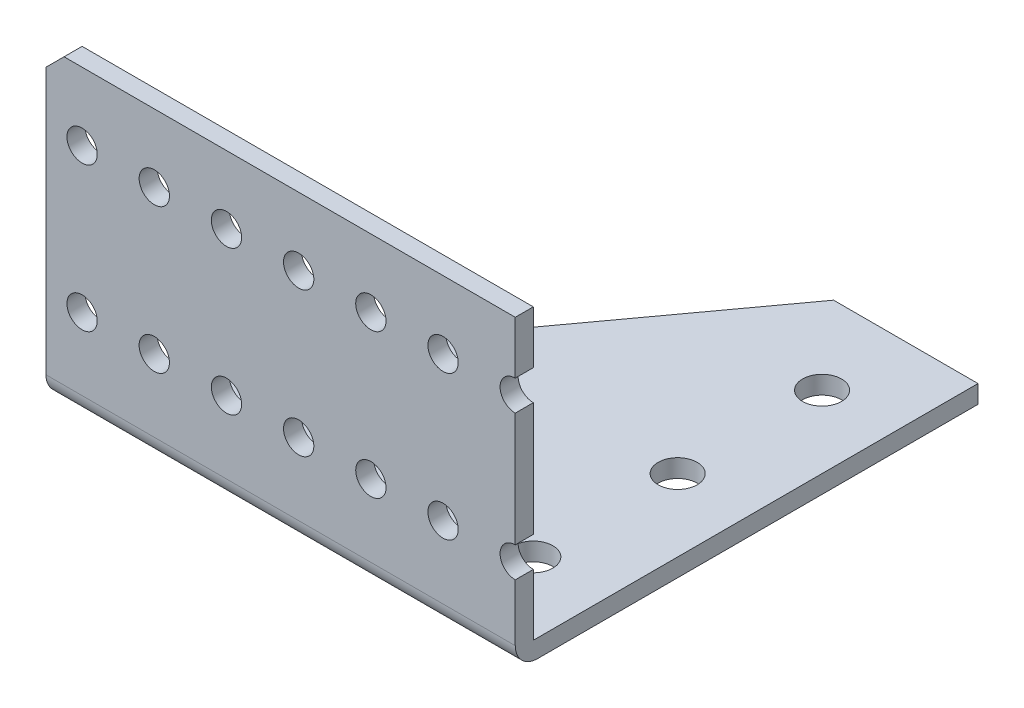
SolidWorks part; units mm, degrees
ref_plane "Front Plane" through (0, 0, 0) normal (0, 0, 1) x (1, 0, 0)
ref_plane "Top Plane" through (0, 0, 0) normal (0, 1, 0) x (1, 0, 0)
ref_plane "Right Plane" through (0, 0, 0) normal (1, 0, 0) x (0, 0, -1)
sketch "Sketch1" plane through (0, 0, 0) normal (0, 1, 0) x (1, 0, 0)
  line L0 (41.275, -40.7035) -> (41.275, 40.7035)
  line L1 (41.275, 40.7035) -> (-41.275, 40.7035)
  line L3 (-41.275, -40.7035) -> (-41.275, 40.7035)
  line L4 (-41.275, -40.7035) -> (41.275, -40.7035)
  line L5 (41.275, 40.7035) -> (-41.275, -40.7035) construction
  line L6 (0, -55) -> (0, 55) construction
  line L7 (-55, 0) -> (55, 0) construction
  point P2 (0, 0)
  dimension "D2" = 81.407
  dimension "D1" = 82.55
extrude "Boss-Extrude1" add sketch "Sketch1" along normal blind 3.175 from offset 34.925 offset against normal yes
sketch "Sketch3" plane through (0, -31.75, 0) normal (0, 1, 0) x (1, 0, 0)
  line L0 (41.275, -40.7035) -> (-41.275, -40.7035)
  line L1 (-41.275, -40.7035) -> (-41.275, -37.5285)
  line L2 (-41.275, -37.5285) -> (41.275, -37.5285)
  line L3 (-41.275, -40.7035) -> (41.275, -40.7035) construction
  line L4 (41.275, -40.7035) -> (41.275, -37.5285)
  line L5 (-41.275, 40.7035) -> (-41.275, -40.7035) construction
  line L6 (41.275, -40.7035) -> (41.275, 40.7035) construction
  point P0 (0, 0)
  dimension "D1" = 3.175
extrude "Boss-Extrude2" add sketch "Sketch3" along normal blind 50.8
hole_wizard "#10 Clearance Hole2" positions "Sketch7" profile "Sketch6" hole size "#10" standard "ANSI Inch" end condition through all
sketch "Sketch7" plane through (0, 0, -40.7035) normal (0, 0, -1) x (-1, 0, 0)
  line L2 (-41.275, -18.288) -> (34.925, -18.288) construction
  line L5 (-41.275, 7.112) -> (34.925, 7.112) construction
  line L8 (41.275, 19.05) -> (41.275, -31.75) construction
  line L9 (-41.275, 19.05) -> (-41.275, -31.75) construction
  line L10 (-41.275, 19.05) -> (41.275, 19.05) construction
  point P56 (22.225, 7.112)
  point P57 (9.525, 7.112)
  point P58 (-3.175, 7.112)
  point P59 (-15.875, 7.112)
  point P61 (-28.575, 7.112)
  point P118 (22.225, -18.288)
  point P119 (9.525, -18.288)
  point P120 (-3.175, -18.288)
  point P121 (-15.875, -18.288)
  point P123 (-28.575, -18.288)
  point P157 (34.925, 7.112)
  point P159 (34.925, -18.288)
  point P185 (-41.275, 7.112)
  point P189 (-41.275, -18.288)
  point P192 (-28.575, -18.161)
  point P198 (-41.275, -18.161)
  point P199 (-41.275, 7.239)
  point P200 (0, 0)
  point P201 (0, 0)
  dimension "D1" = 6.35
  dimension "D2" = 11.938
  dimension "D3" = 12.7
  dimension "D4" = 25.4
  dimension "D5" = 12.7
  dimension "D6" = 12.7
  dimension "D7" = 12.7
  dimension "D8" = 12.7
  dimension "D10" = 12.7
sketch "Sketch6" plane through (-22.225, 7.112, -40.7035) normal (1, 0, 0) x (0, 1, 0)
  line L0 (0, 0) -> (0, 81.407)
  line L1 (0, 81.407) -> (2.667, 81.407)
  line L2 (2.667, 81.407) -> (2.667, 0)
  line L5 (2.667, 0) -> (0, 0)
  line L11 (0, -6.35) -> (0, 107.95) construction
  dimension "Thru Hole Dia." = 5.334
  dimension "Thru Hole Depth" = 81.407
chamfer "Chamfer1" distance 3.175 angle 45 1 edges at (-41.275, 19.05, 39.116)
fillet "Fillet2" radius 3.937 1 edges at (0, -34.925, 40.7035) tangent propagation no
sketch "Sketch9" plane through (0, -34.925, 0) normal (0, -1, 0) x (1, 0, 0)
  line L0 (-41.275, 37.5285) -> (15.875, -40.7035)
  line L1 (-41.275, -40.7035) -> (-41.275, 36.7665) construction
  line L2 (41.275, -40.7035) -> (-41.275, -40.7035) construction
  line L3 (41.275, 36.7665) -> (41.275, -40.7035) construction
  line L4 (15.875, -40.7035) -> (-41.275, -40.7035)
  line L5 (-41.275, -40.7035) -> (-41.275, 37.5285)
  line L6 (-41.275, 40.7035) -> (41.275, 40.7035) construction
  line L7 (28.575, -40.7035) -> (28.575, 36.7665) construction
  line L8 (41.275, 36.7665) -> (-41.275, 36.7665) construction
  line L9 (41.275, 37.5285) -> (-41.275, 37.5285) construction
  circle A0 centre (34.925, 23.9395) radius 3.429 construction
  circle A1 centre (34.925, 11.2395) radius 3.429 construction
  circle A2 centre (34.925, -1.4605) radius 3.429 construction
  circle A3 centre (28.575, 24.8285) radius 3.429
  circle A7 centre (28.575, -0.5715) radius 3.429
  circle A8 centre (28.575, -25.9715) radius 3.429
  point P26 (-41.275, 37.5285)
  point P27 (0, 0)
  dimension "D3" = 6.858
  dimension "D7" = 16.764
  dimension "D9" = 6.858
  dimension "D10" = 12.7
  dimension "D11" = 3
  dimension "D12" = 25.4
  dimension "D1" = 25.4
  dimension "D2" = 0
  dimension "D4" = 12.7
  dimension "D5" = 12.7
  dimension "D6" = 6.35
  dimension "D8" = 12.7
extrude "Cut-Extrude2" cut sketch "Sketch9" against normal through all
